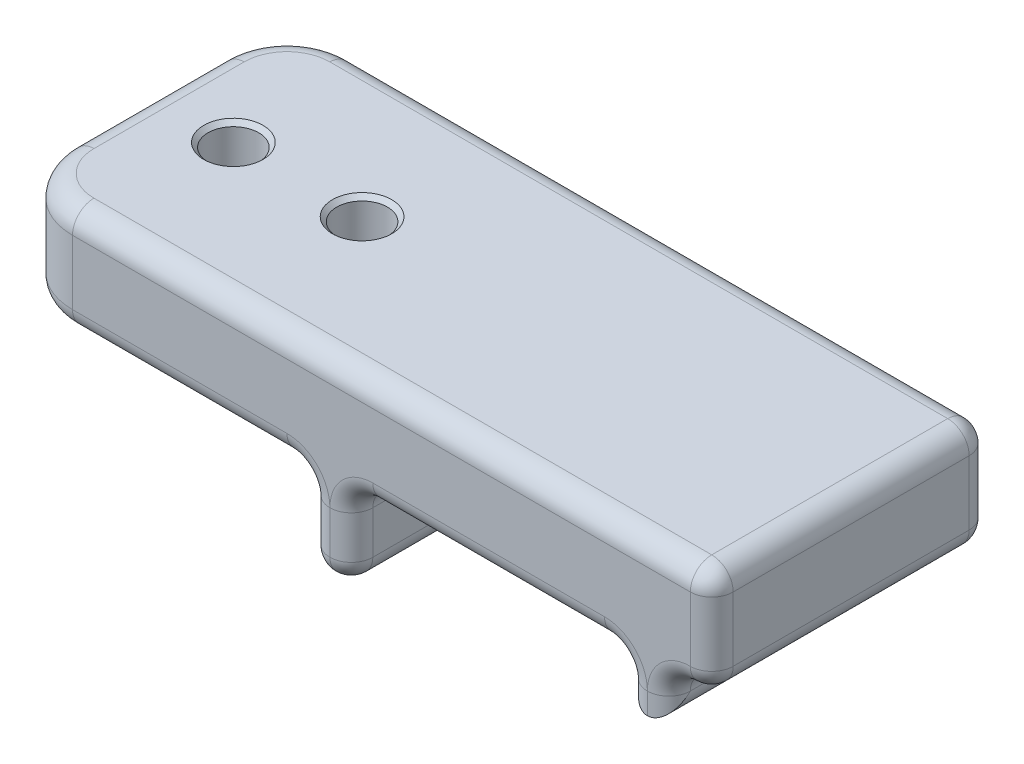
SolidWorks part; units mm, degrees
ref_plane "Front Plane" through (0, 0, 0) normal (0, 0, 1) x (1, 0, 0)
ref_plane "Top Plane" through (0, 0, 0) normal (0, 1, 0) x (1, 0, 0)
ref_plane "Right Plane" through (0, 0, 0) normal (1, 0, 0) x (0, 0, -1)
sketch "Sketch1" plane through (0, 0, 0) normal (0, 1, 0) x (1, 0, 0)
  line L1 (0, 0) -> (41.656, 0)
  line L2 (0, 0) -> (0, 16.51)
  line L3 (0, 16.51) -> (41.656, 16.51)
  line L4 (41.656, 0) -> (41.656, 16.51)
  dimension "D1" = 41.656
  dimension "D2" = 16.51
extrude "Boss-Extrude1" add sketch "Sketch1" along normal blind 6.35
sketch "Sketch2" plane through (0, 0, 0) normal (0, -1, 0) x (1, 0, 0)
  line L0 (0, 0) -> (41.656, 0) construction
  line L1 (39.116, 0) -> (36.576, 0)
  line L2 (39.116, 0) -> (39.116, -16.51)
  line L3 (39.116, -16.51) -> (36.576, -16.51)
  line L4 (36.576, 0) -> (36.576, -16.51)
  line L5 (41.656, -16.51) -> (0, -16.51) construction
  line L6 (41.656, 0) -> (41.656, -16.51) construction
  dimension "D1" = 2.54
  dimension "D2" = 2.54
extrude "Boss-Extrude2" add sketch "Sketch2" along normal blind 2.54
sketch "Sketch3" plane through (0, 0, 0) normal (0, -1, 0) x (1, 0, 0)
  line L0 (36.576, -16.51) -> (0, -16.51) construction
  line L1 (20.32, 0) -> (17.78, 0)
  line L2 (20.32, 0) -> (20.32, -16.51)
  line L3 (20.32, -16.51) -> (17.78, -16.51)
  line L4 (17.78, 0) -> (17.78, -16.51)
  line L5 (36.576, 0) -> (36.576, -16.51) construction
  dimension "D1" = 2.54
  dimension "D2" = 16.256
extrude "Boss-Extrude3" add sketch "Sketch3" along normal blind 5.08
hole_wizard "Ø3.0mm Dowel Hole1" positions "Sketch5" profile "Sketch4" hole size "Ø3.0" standard "ISO" end condition through all
sketch "Sketch5" plane through (0, 6.35, 0) normal (0, 1, 0) x (1, 0, 0)
  line L0 (0, 0) -> (41.656, 0) construction
  line L1 (0, 16.51) -> (0, 0) construction
  point P0 (5.08, 8.255)
  point P2 (12.7, 8.255)
  dimension "D1" = 8.255
  dimension "D2" = 5.08
  dimension "D3" = 7.62
sketch "Sketch4" plane through (5.08, 6.35, -8.255) normal (1, 0, 0) x (0, 0, 1)
  line L0 (0, 0) -> (0, 11.43)
  line L1 (0, 11.43) -> (1.5, 11.43)
  line L2 (1.5, 11.43) -> (1.5, 0)
  line L5 (1.5, 0) -> (0, 0)
  line L11 (0, -6.35) -> (0, 107.95) construction
  dimension "Thru Hole Dia." = 3
  dimension "Thru Hole Depth" = 11.43
fillet "Fillet1" radius 1.27 28 edges at (17.78, 0, -8.255) (17.78, -5.08, -8.255) (20.32, -5.08, -8.255) (39.116, -2.54, -8.255) (41.656, 6.35, -8.255) (41.656, 0, -8.255) (41.656, 3.175, -16.51) (20.828, 6.35, -16.51) (17.78, -2.54, -16.51) (20.32, -2.54, -16.51) (20.32, 0, -8.255) (0, 6.35, -8.255) (0, 0, -8.255) (20.828, 6.35, 0) (41.656, 3.175, 0) (20.32, -2.54, 0) (17.78, -2.54, 0) (36.576, -2.54, -8.255)
chamfer "Chamfer1" distance 0.254 angle 45 4 edges at (12.7, 6.35, -6.755) (5.08, 6.35, -6.755) (5.08, 0, -9.755) (12.7, 0, -9.755)
fillet "Fillet2" radius 3.81 6 edges at (0.372, 0.372, -16.138) (0.372, 5.978, -16.138) (0.372, 0.372, -0.372) (0.372, 5.978, -0.372) (0, 3.175, 0) (0, 3.175, -16.51)
